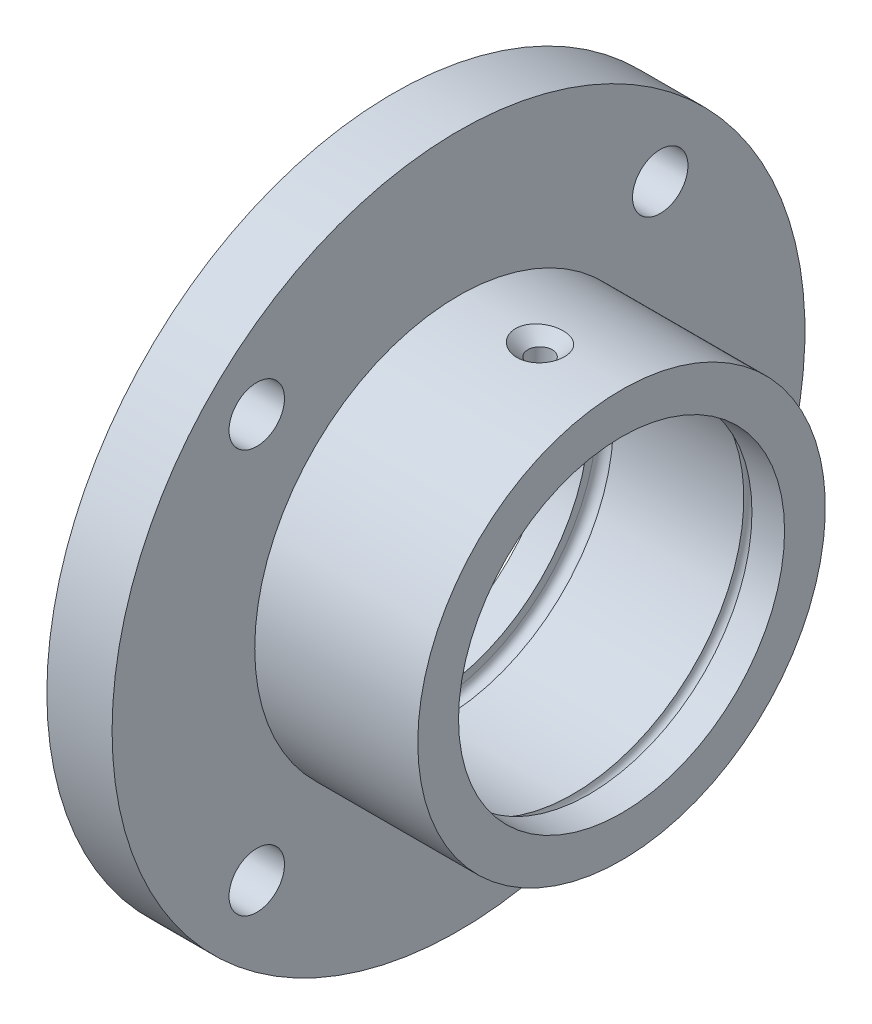
SolidWorks part; units mm, degrees
ref_plane "前视基准面" through (0, 0, 0) normal (0, 0, 1) x (1, 0, 0)
ref_plane "上视基准面" through (0, 0, 0) normal (0, 1, 0) x (1, 0, 0)
ref_plane "右视基准面" through (0, 0, 0) normal (1, 0, 0) x (0, 0, -1)
sketch "草图1" plane through (0, 0, 0) normal (0, 0, 1) x (1, 0, 0)
  line L0 (0, 0) -> (28, 0) construction
  line L1 (55, 0) -> (-55, 0) construction
  line L2 (0, 0) -> (0, 42.5)
  line L3 (0, -55) -> (0, 55) construction
  line L4 (0, 42.5) -> (8, 42.5)
  line L5 (8, 42.5) -> (8, 25)
  line L6 (8, 25) -> (28, 25)
  line L7 (28, 25) -> (28, 0)
  line L8 (0, 0) -> (28, 0)
  dimension "D1" = 28
  dimension "D2" = 50
  dimension "D3" = 85
  dimension "D4" = 8
revolve "旋转1" add sketch "草图1" angle 360 about L0
sketch "草图2" plane through (0, 0, 0) normal (0, 0, 1) x (1, 0, 0)
  line L0 (0, 0) -> (28, 0) construction
  line L1 (28, -25) -> (28, 25) construction
  line L2 (0, 0) -> (0, 20)
  line L3 (0, -46.75) -> (0, 46.75) construction
  line L4 (0, 20) -> (4, 20)
  line L5 (4, 20) -> (4, 21)
  line L6 (0, 0) -> (28, 0)
  line L8 (6, 21) -> (22, 21)
  line L11 (24, 21) -> (24, 20)
  line L12 (24, 20) -> (28, 20)
  line L13 (28, 20) -> (28, 0)
  arc A0 (6, 21) -> (4, 21) centre (5, 21) ccw
  arc A1 (24, 21) -> (22, 21) centre (23, 21) ccw
  dimension "D6" = 2
  dimension "D7" = 2
  dimension "D1" = 40
  dimension "D2" = 42
  dimension "D3" = 40
  dimension "D4" = 4
  dimension "D5" = 4
revolve "切除-旋转1" cut sketch "草图2" angle 360 about L0
ref_plane "基准面1" through (0, 25, 0) normal (0, 1, 0) x (1, 0, 0)
sketch "草图3" plane through (0, 25, 0) normal (0, 1, 0) x (1, 0, 0)
  line L0 (-15.4, 0) -> (15.4, 0) construction
  line L1 (28, -25) -> (28, 25) construction
  point P0 (18, 0)
  dimension "D1" = 10
hole_wizard "Ø3.0mm 暗销孔1" positions "草图3" profile "草图4" hole size "Ø3.0" standard "GB" end condition up to next
sketch "草图4" plane through (18, 25, 0) normal (1, 0, 0) x (0, 0, 1)
  line L0 (0, 0) -> (0, 4)
  line L1 (0, 4) -> (1.5, 4)
  line L2 (1.5, 4) -> (1.5, 1.5)
  line L3 (1.5, 1.5) -> (3, 0)
  line L5 (3, 0) -> (0, 0)
  line L6 (-1.5, 1.5) -> (-3, 0) construction
  line L11 (0, -6.35) -> (0, 107.95) construction
  dimension "通孔孔直径" = 3
  dimension "通孔孔深度" = 4
  dimension "近端锥形沉头孔直径" = 6
  dimension "近端锥形沉头孔角度" = 90
sketch "草图5" plane through (0, 0, 0) normal (-1, 0, 0) x (0, 0, 1)
  line L0 (0, 0) -> (24.7487, 24.7487) construction
  line L1 (15.4, 0) -> (-15.4, 0) construction
  point P1 (24.7487, 24.7487)
  dimension "D1" = 45
  dimension "D2" = 35
hole_wizard "M8 螺纹孔1" positions "草图5" profile "草图6" tap size "M8" standard "GB" end condition through all
sketch "草图6" plane through (0, 24.7487, 24.7487) normal (0, 1, 0) x (0, 0, 1)
  line L0 (0, 0) -> (0, 28)
  line L1 (0, 28) -> (3.4, 28)
  line L2 (3.4, 28) -> (3.4, 0.625)
  line L3 (3.4, 0.625) -> (4.025, 0)
  line L5 (4.025, 0) -> (0, 0)
  line L6 (-3.4, 0.625) -> (-4.025, 0) construction
  line L11 (0, -6.35) -> (0, 107.95) construction
  dimension "通孔螺纹孔钻头直径" = 6.8
  dimension "通孔螺纹孔钻头深度" = 28
  dimension "近端锥形沉头孔直径" = 8.05
  dimension "近端锥形沉头孔角度" = 90
cosmetic thread "孔螺纹线1" parameters "D2"=8
pattern_circular "阵列(圆周)1" count 4 over 360 about axis through (0, 0, 0) along (-1, 0, 0) of "M8 螺纹孔1"
cosmetic thread "孔螺纹线2" parameters "D2"=8
cosmetic thread "孔螺纹线3" parameters "D2"=8
cosmetic thread "孔螺纹线4" parameters "D2"=8
